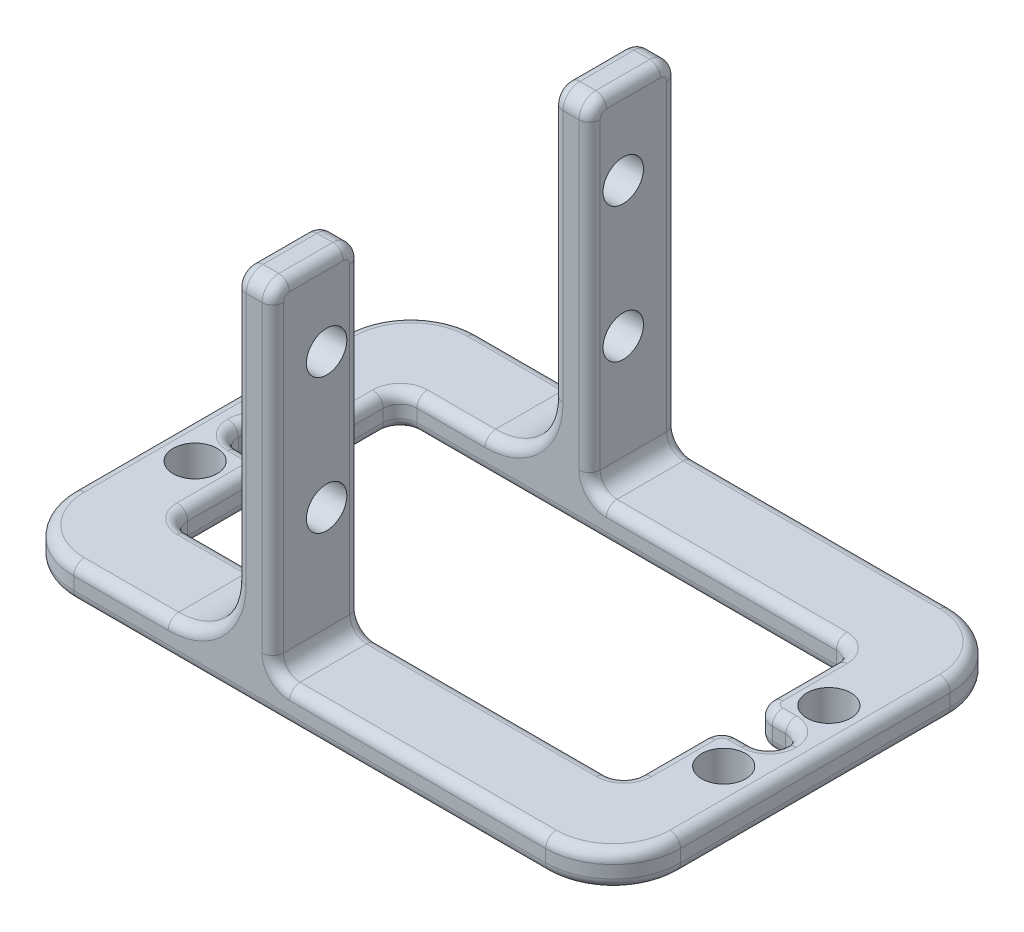
SolidWorks part; units mm, degrees
ref_plane "Front Plane" through (0, 0, 0) normal (0, 0, 1) x (1, 0, 0)
ref_plane "Top Plane" through (0, 0, 0) normal (0, 1, 0) x (1, 0, 0)
ref_plane "Right Plane" through (0, 0, 0) normal (1, 0, 0) x (0, 0, -1)
sketch "Sketch1" plane through (0, 0, 0) normal (0, 1, 0) x (1, 0, 0)
  line L1 (-28.575, -19.05) -> (28.575, -19.05)
  line L2 (-28.575, -19.05) -> (-28.575, 19.05)
  line L3 (-28.575, 19.05) -> (28.575, 19.05)
  line L4 (28.575, -19.05) -> (28.575, 19.05)
  line L5 (-28.575, -19.05) -> (28.575, 19.05) construction
  line L6 (-28.575, 19.05) -> (28.575, -19.05) construction
  point P0 (0, 0)
  dimension "D1" = 38.1
  dimension "D2" = 57.15
extrude "Boss-Extrude1" add sketch "Sketch1" along normal blind 3.175
sketch "Sketch2" plane through (0, 3.175, 0) normal (0, 1, 0) x (1, 0, 0)
  line L0 (0, 0) -> (-28.575, 0) construction
  line L1 (-24.892, -4.953) -> (24.892, -4.953) construction
  line L2 (-24.892, -4.953) -> (-24.892, 4.953) construction
  line L3 (-24.892, 4.953) -> (24.892, 4.953) construction
  line L4 (24.892, -4.953) -> (24.892, 4.953) construction
  line L5 (-24.892, -4.953) -> (24.892, 4.953) construction
  line L6 (-24.892, 4.953) -> (24.892, -4.953) construction
  line L7 (-21.336, -10.795) -> (21.336, -10.795)
  line L8 (-21.336, -10.795) -> (-21.336, 10.795) construction
  line L9 (-21.336, 10.795) -> (21.336, 10.795)
  line L10 (21.336, -10.795) -> (21.336, 10.795) construction
  line L11 (-21.336, -10.795) -> (21.336, 10.795) construction
  line L12 (-21.336, 10.795) -> (21.336, -10.795) construction
  line L13 (-28.575, 19.05) -> (-28.575, -19.05) construction
  line L14 (-28.575, 0) -> (28.575, 0) construction
  line L15 (28.575, -19.05) -> (28.575, 19.05) construction
  line L16 (21.336, -1.5875) -> (21.336, -10.795)
  line L17 (25.781, -1.5875) -> (21.336, -1.5875)
  line L18 (25.781, -1.5875) -> (25.781, 1.5875)
  line L19 (25.781, 1.5875) -> (21.336, 1.5875)
  line L20 (21.336, -1.5875) -> (21.336, 1.5875) construction
  line L21 (25.781, -1.5875) -> (21.336, 1.5875) construction
  line L22 (25.781, 1.5875) -> (21.336, -1.5875) construction
  line L23 (-25.781, -1.5875) -> (-21.336, -1.5875)
  line L24 (-25.781, -1.5875) -> (-25.781, 1.5875)
  line L25 (-25.781, 1.5875) -> (-21.336, 1.5875)
  line L26 (-21.336, -1.5875) -> (-21.336, 1.5875) construction
  line L27 (-25.781, -1.5875) -> (-21.336, 1.5875) construction
  line L28 (-25.781, 1.5875) -> (-21.336, -1.5875) construction
  line L29 (21.336, 1.5875) -> (21.336, 10.795)
  line L30 (-21.336, -10.795) -> (-21.336, -1.5875)
  line L31 (-21.336, 1.5875) -> (-21.336, 10.795)
  circle A0 centre (-24.892, -4.953) radius 2.0701
  circle A1 centre (-24.892, 4.953) radius 2.0701
  circle A2 centre (24.892, 4.953) radius 2.0701
  circle A3 centre (24.892, -4.953) radius 2.0701
  point P0 (0, 0)
  point P10 (0, 0)
  point P19 (23.5585, 0)
  point P27 (-23.5585, 0)
  dimension "D3" = 4.1402
  dimension "D1" = 49.784
  dimension "D2" = 9.906
  dimension "D4" = 42.672
  dimension "D5" = 21.59
  dimension "D6" = 4.445
  dimension "D7" = 4.445
  dimension "D8" = 3.175
  dimension "D9" = 3.175
extrude "Cut-Extrude1" cut sketch "Sketch2" against normal through all
sketch "Sketch3" plane through (0, 3.175, 0) normal (0, 1, 0) x (1, 0, 0)
  line L0 (-28.575, -19.05) -> (28.575, -19.05) construction
  line L1 (-6.985, -19.05) -> (-3.4925, -19.05)
  line L2 (-6.985, -19.05) -> (-6.985, -10.795)
  line L3 (-6.985, -10.795) -> (-3.4925, -10.795)
  line L4 (-3.4925, -19.05) -> (-3.4925, -10.795)
  line L5 (-21.336, -10.795) -> (21.336, -10.795) construction
  line L6 (21.336, 10.795) -> (-21.336, 10.795) construction
  line L7 (-6.985, 10.795) -> (-3.4925, 10.795)
  line L8 (-6.985, 10.795) -> (-6.985, 19.05)
  line L9 (-6.985, 19.05) -> (-3.4925, 19.05)
  line L10 (-3.4925, 10.795) -> (-3.4925, 19.05)
  line L11 (28.575, 19.05) -> (-28.575, 19.05) construction
  line L12 (-28.575, 19.05) -> (-28.575, -19.05) construction
  dimension "D1" = 21.59
  dimension "D2" = 3.4925
extrude "Boss-Extrude2" add sketch "Sketch3" along normal blind 31.75
sketch "Sketch4" plane through (-6.985, 0, 0) normal (-1, 0, 0) x (0, 0, 1)
  line L0 (13.97, 3.175) -> (13.97, 34.925) construction
  line L1 (10.795, 3.175) -> (19.05, 3.175) construction
  line L2 (10.795, 34.925) -> (19.05, 34.925) construction
  line L3 (-13.97, 34.925) -> (-13.97, 3.175) construction
  line L4 (-19.05, 34.925) -> (-10.795, 34.925) construction
  line L5 (-19.05, 3.175) -> (-10.795, 3.175) construction
  line L6 (0, 0) -> (0, -50000) construction
  line L7 (13.97, 19.05) -> (0, 19.05) construction
  line L8 (0, 19.05) -> (-13.97, 19.05) construction
  circle A0 centre (13.97, 27.305) radius 1.905
  circle A1 centre (-13.97, 27.305) radius 1.905
  circle A2 centre (-13.97, 14.605) radius 1.905
  circle A3 centre (13.97, 14.605) radius 1.905
  dimension "D2" = 3.81
  dimension "D1" = 27.94
  dimension "D3" = 12.7
  dimension "D4" = 11.43
extrude "Cut-Extrude2" cut sketch "Sketch4" against normal through all
fillet "Fillet1" radius 1.5875 18 edges at (-3.4925, 3.175, -14.9225) (-21.336, 1.5875, -10.795) (-21.336, 1.5875, 10.795) (-21.336, 1.5875, -1.5875) (-21.336, 1.5875, 1.5875) (-25.781, 1.5875, 1.5875) (-25.781, 1.5875, -1.5875) (21.336, 1.5875, -10.795) (21.336, 1.5875, -1.5875) (25.781, 1.5875, -1.5875) (25.781, 1.5875, 1.5875) (21.336, 1.5875, 1.5875) (21.336, 1.5875, 10.795) (-5.2387, 34.925, -10.795) (-5.2387, 34.925, -19.05) (-5.2387, 34.925, 19.05) (-5.2387, 34.925, 10.795)
fillet "Fillet2" radius 6.35 6 edges at (-6.985, 3.175, -14.9225) (28.575, 1.5875, 19.05) (28.575, 1.5875, -19.05) (-28.575, 1.5875, -19.05) (-28.575, 1.5875, 19.05)
fillet "Fillet3" radius 1 92 edges at (-26.7151, 0, 17.1901) (-28.575, 0, 0) (-26.7151, 0, -17.1901) (0, 0, -19.05) (26.7151, 0, -17.1901) (28.575, 0, 0) (26.7151, 0, 17.1901) (0, 0, 19.05) (-6.985, 21.4312, -19.05) (-8.8449, 5.0349, -19.05) (-8.8449, 5.0349, 19.05) (-26.7151, 3.175, 17.1901) (-28.575, 3.175, 0) (-26.7151, 3.175, -17.1901) (-3.0275, 3.64, 19.05) (26.7151, 3.175, 17.1901) (28.575, 3.175, 0) (26.7151, 3.175, -17.1901) (-3.4925, 19.05, -19.05) (-3.0275, 3.64, -19.05) (-6.985, 21.4312, -10.795) (-8.8449, 5.0349, -10.795) (-16.5417, 3.175, -10.795) (-20.871, 3.175, -10.33) (-21.336, 3.175, -6.1912) (-21.801, 3.175, -2.0525) (-23.5585, 3.175, -1.5875) (-25.316, 3.175, -1.1225) (-25.316, 3.175, 1.1225) (-23.5585, 3.175, 1.5875) (-21.801, 3.175, 2.0525) (-21.336, 3.175, 6.1913) (-20.871, 3.175, 10.33) (-8.8449, 5.0349, 10.795) (-3.0275, 3.64, 10.795) (-3.4925, 19.05, -10.795) (-3.0275, 3.64, -10.795) (8.9218, 3.175, -10.795) (20.871, 3.175, -10.33) (21.336, 3.175, -6.1913) (21.801, 3.175, -2.0525) (23.5585, 3.175, -1.5875) (25.316, 3.175, -1.1225) (25.316, 3.175, 1.1225) (23.5585, 3.175, 1.5875) (21.801, 3.175, 2.0525) (21.336, 3.175, 6.1912) (20.871, 3.175, 10.33) (-20.871, 0, 10.33) (-21.336, 0, 6.1913) (-21.801, 0, 2.0525) (-23.5585, 0, 1.5875) (-25.316, 0, 1.1225) (-25.316, 0, -1.1225) (-23.5585, 0, -1.5875) (-21.801, 0, -2.0525) (-21.336, 0, -6.1912) (-20.871, 0, -10.33) (0, 0, -10.795) (20.871, 0, -10.33) (21.336, 0, -6.1913) (21.801, 0, -2.0525) (23.5585, 0, -1.5875) (25.316, 0, -1.1225) (25.316, 0, 1.1225) (23.5585, 0, 1.5875) (21.801, 0, 2.0525) (21.336, 0, 6.1912) (20.871, 0, 10.33) (-17.78, 3.175, -19.05) (10.16, 3.175, -19.05) (0, 0, 10.795) (-6.985, 34.46, -11.26) (-6.985, 34.925, -14.9225) (-6.985, 34.46, -18.585) (-6.985, 34.46, 18.585) (-6.985, 34.925, 14.9225) (-6.985, 34.46, 11.26) (-3.4925, 34.46, 11.26) (-3.4925, 34.925, 14.9225) (-3.4925, 34.46, 18.585) (-3.4925, 34.46, -18.585) (-3.4925, 34.925, -14.9225) (-3.4925, 34.46, -11.26)
